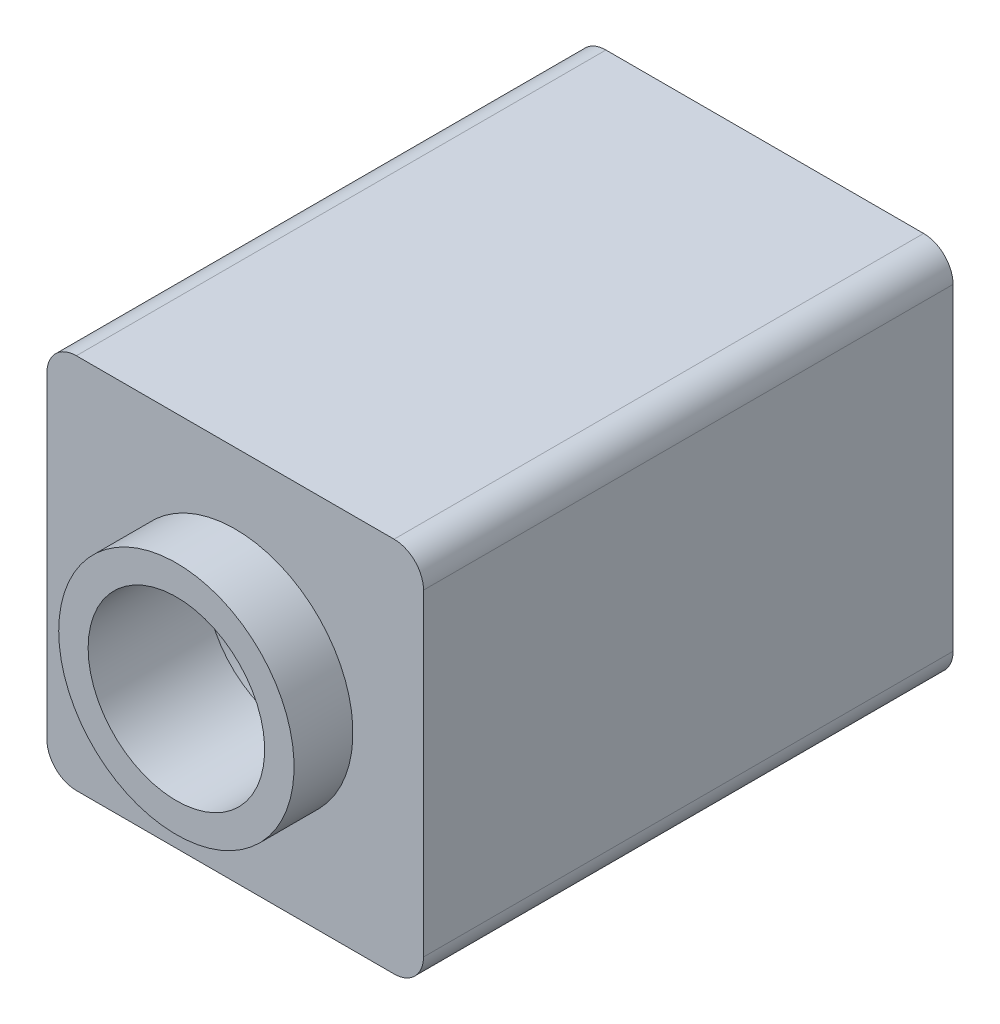
SolidWorks part; units mm, degrees
ref_plane "Front Plane" through (0, 0, 0) normal (0, 0, 1) x (1, 0, 0)
ref_plane "Top Plane" through (0, 0, 0) normal (0, 1, 0) x (1, 0, 0)
ref_plane "Right Plane" through (0, 0, 0) normal (1, 0, 0) x (0, 0, -1)
sketch "Sketch2" plane through (0, 0, -57.4655) normal (0, 0, -1) x (-1, 0, 0)
  line L1 (-6.4405, -35.0284) -> (-1.0405, -35.0284)
  line L2 (-6.9405, -34.5284) -> (-6.9405, -29.1284)
  line L3 (-6.4405, -28.6284) -> (-1.0405, -28.6284)
  line L4 (-0.5405, -34.5284) -> (-0.5405, -29.1284)
  line L5 (-6.9405, -35.0284) -> (-0.5405, -28.6284) construction
  line L6 (-6.9405, -28.6284) -> (-0.5405, -35.0284) construction
  circle A0 centre (-3.7405, -31.8284) radius 1.5
  arc A1 (-0.5405, -34.5284) -> (-1.0405, -35.0284) centre (-1.0405, -34.5284) cw
  arc A2 (-6.9405, -34.5284) -> (-6.4405, -35.0284) centre (-6.4405, -34.5284) ccw
  arc A3 (-6.9405, -29.1284) -> (-6.4405, -28.6284) centre (-6.4405, -29.1284) cw
  arc A4 (-0.5405, -29.1284) -> (-1.0405, -28.6284) centre (-1.0405, -29.1284) ccw
  point P0 (-3.7405, -31.8284)
  dimension "D2" = 3
  dimension "D3" = 0.5
  dimension "D1" = 6.4
extrude "Boss-Extrude1" add sketch "Sketch2" along normal blind 10
sketch "Sketch3" plane through (0, 0, -57.4655) normal (0, 0, -1) x (-1, 0, 0)
  line L4 (-1.0405, -28.6284) -> (-6.4405, -28.6284)
  line L5 (-6.9405, -29.1284) -> (-6.9405, -34.5284)
  line L6 (-6.4405, -35.0284) -> (-1.0405, -35.0284)
  line L7 (-0.5405, -34.5284) -> (-0.5405, -29.1284)
  line L8 (-1.0405, -28.6284) -> (-6.4405, -28.6284)
  line L9 (-6.9405, -29.1284) -> (-6.9405, -34.5284)
  line L10 (-6.4405, -35.0284) -> (-1.0405, -35.0284)
  line L11 (-0.5405, -34.5284) -> (-0.5405, -29.1284)
  circle A1 centre (-3.7405, -31.8284) radius 5 construction
  circle A2 centre (-3.7405, -31.8284) radius 2
  arc A6 (-6.4405, -28.6284) -> (-6.9405, -29.1284) centre (-6.4405, -29.1284) ccw
  arc A7 (-6.9405, -34.5284) -> (-6.4405, -35.0284) centre (-6.4405, -34.5284) ccw
  arc A8 (-1.0405, -35.0284) -> (-0.5405, -34.5284) centre (-1.0405, -34.5284) ccw
  arc A9 (-0.5405, -29.1284) -> (-1.0405, -28.6284) centre (-1.0405, -29.1284) ccw
  arc A10 (-6.4405, -28.6284) -> (-6.9405, -29.1284) centre (-6.4405, -29.1284) ccw
  arc A11 (-6.9405, -34.5284) -> (-6.4405, -35.0284) centre (-6.4405, -34.5284) ccw
  arc A12 (-1.0405, -35.0284) -> (-0.5405, -34.5284) centre (-1.0405, -34.5284) ccw
  arc A13 (-0.5405, -29.1284) -> (-1.0405, -28.6284) centre (-1.0405, -29.1284) ccw
  dimension "D1" = 4
  dimension "D2" = 0
extrude "Cut-Extrude1" cut sketch "Sketch3" along normal blind 1
sketch "Sketch4" plane through (0, 0, -67.4655) normal (0, 0, -1) x (-1, 0, 0)
  circle A0 centre (-3.7405, -31.8284) radius 2.4
extrude "Cut-Extrude2" cut sketch "Sketch4" against normal blind 8
